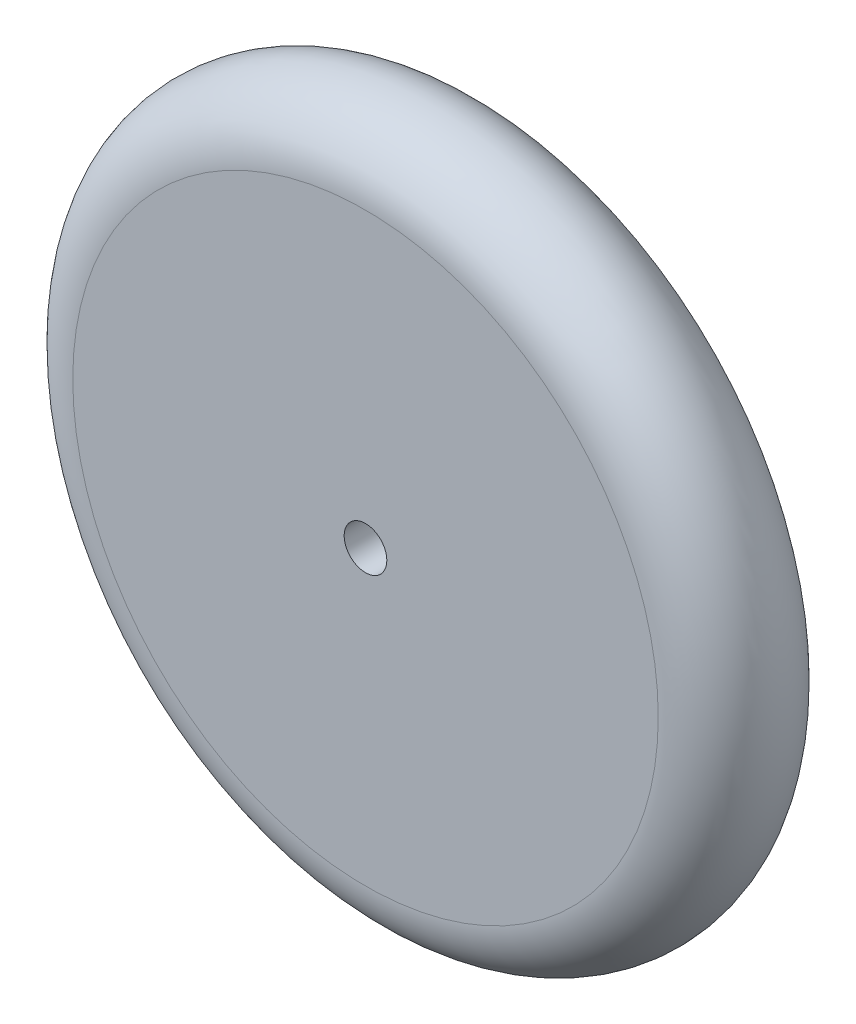
SolidWorks part; units mm, degrees
ref_plane "Front Plane" through (0, 0, 0) normal (0, 0, 1) x (1, 0, 0)
ref_plane "Top Plane" through (0, 0, 0) normal (0, 1, 0) x (1, 0, 0)
ref_plane "Right Plane" through (0, 0, 0) normal (1, 0, 0) x (0, 0, -1)
sketch "Sketch1" plane through (0, 0, 0) normal (0, 0, 1) x (1, 0, 0)
  circle A0 centre (0, 0) radius 158.75
  circle A1 centre (0, 0) radius 9.525
  dimension "D1" = 317.5
  dimension "D2" = 19.05
extrude "Boss-Extrude1" add sketch "Sketch1" along normal blind 55.88
fillet "Fillet1" 2 edges at (158.75, 0, 55.88) (158.75, 0, 0) type full round first side face at (158.75, 0, 55.88) second side face at (158.75, 0, 0) middle face at (158.75, 0, 55.88)
